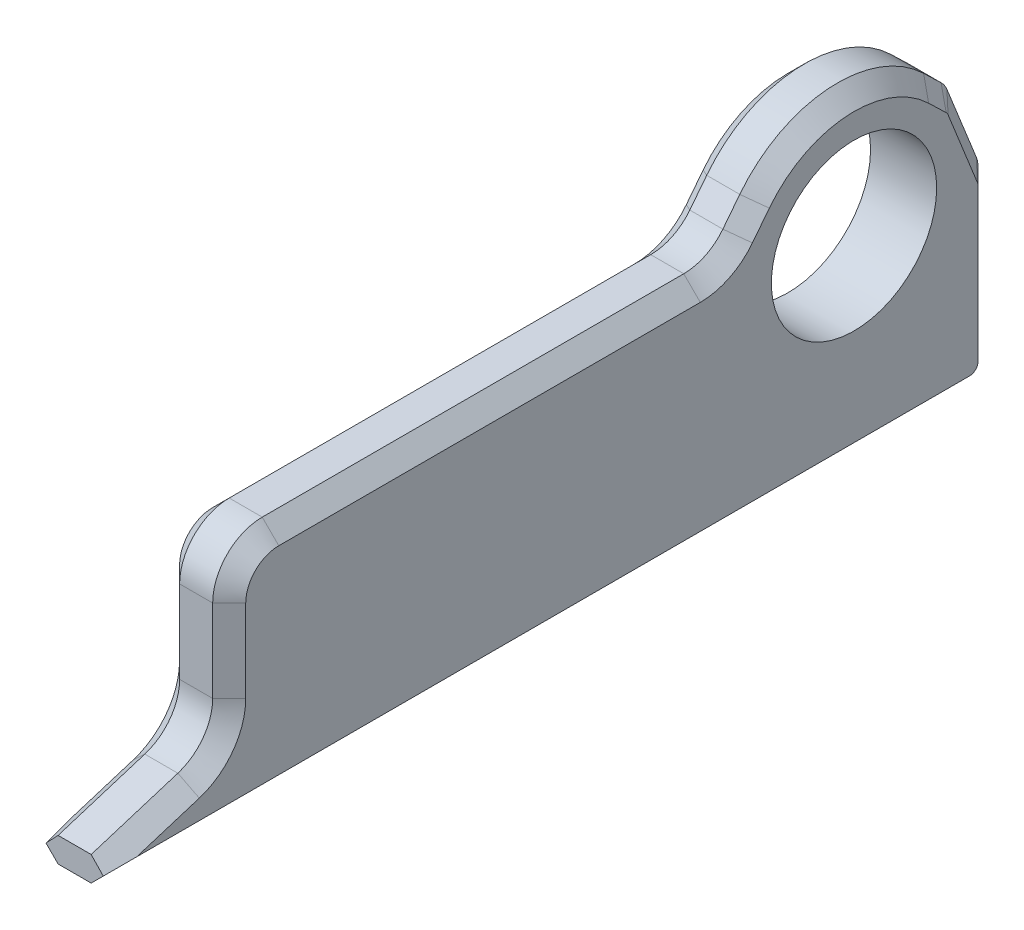
SolidWorks part; units mm, degrees
material "Q355"
ref_plane "前视基准面" through (0, 0, 0) normal (0, 0, 1) x (1, 0, 0)
ref_plane "上视基准面" through (0, 0, 0) normal (0, 1, 0) x (1, 0, 0)
ref_plane "右视基准面" through (0, 0, 0) normal (1, 0, 0) x (0, 0, -1)
sketch "草图1" plane through (0, 0, 0) normal (1, 0, 0) x (0, 0, -1)
  line L1 (85, -8.5) -> (65, 41.5)
  line L2 (65, 41.5) -> (52.0831, 53.9662)
  line L3 (-59.1242, 46.1447) -> (-69.3503, 33.0421)
  line L4 (-93, 21.5) -> (-348, 21.5)
  line L5 (-378, -8.5) -> (-378, -58.5)
  line L6 (-399.0641, -87.1382) -> (-451.5009, -103.5)
  line L7 (-451.5009, -103.5) -> (-451.5009, -118.5)
  line L8 (-451.5009, -118.5) -> (-116.5009, -118.5)
  line L10 (-116.5009, -118.5) -> (85, -118.5)
  line L11 (85, -118.5) -> (85, -8.5)
  circle A0 centre (0, 0) radius 50
  arc A3 (52.0831, 53.9662) -> (-59.1242, 46.1447) centre (0, 0) ccw
  arc A4 (-93, 21.5) -> (-69.3503, 33.0421) centre (-93, 51.5) ccw
  arc A5 (-348, 21.5) -> (-378, -8.5) centre (-348, -8.5) ccw
  arc A6 (-399.0641, -87.1382) -> (-378, -58.5) centre (-408, -58.5) ccw
  dimension "D1" = 100
  dimension "D2" = 85
  dimension "D3" = 50
  dimension "D4" = 75
  dimension "D5" = 30
  dimension "D6" = 110
  dimension "D7" = 118.5
  dimension "D13" = 15
  dimension "D8" = 73.5009
  dimension "D16" = 50
  dimension "D9" = 335
  dimension "D11" = 378
  dimension "D12" = 140
  dimension "D14" = 255
  dimension "D15" = 20
extrude "凸台-拉伸1" add sketch "草图1" along normal blind 40
fillet "圆角1" radius 15 1 edges at (20, -118.5, -85)
fillet "圆角2" radius 15 2 edges at (20, 41.5, -65) (20, -8.5, -85)
chamfer "倒角1" distance 10 angle 45 30 edges at (40, -118.5, 190.7505) (0, -118.5, 190.7505) (40, -95.3191, 425.2825) (40, -76.2753, 383.8331) (40, -33.5, 378) (40, 12.7132, 369.2132) (40, 21.5, 220.5) (40, 24.5395, 79.842) (40, 39.5934, 64.2373) (40, 74.8152, 5.2619) (40, 48.8504, -57.3839) (40, 41.3096, -64.7168) (40, 16.3472, -75.0611) (40, -8.5521, -84.7293) (40, -57.4444, -85) (40, -114.1066, -80.6066) (0, -95.3191, 425.2825) (0, -76.2753, 383.8331) (0, -33.5, 378) (0, 12.7132, 369.2132) (0, 21.5, 220.5) (0, 24.5395, 79.842) (0, 39.5934, 64.2373) (0, 74.8152, 5.2619) (0, 48.8504, -57.3839) (0, 41.3096, -64.7168) (0, 16.3472, -75.0611) (0, -8.5521, -84.7293) (0, -57.4444, -85) (0, -114.1066, -80.6066)
